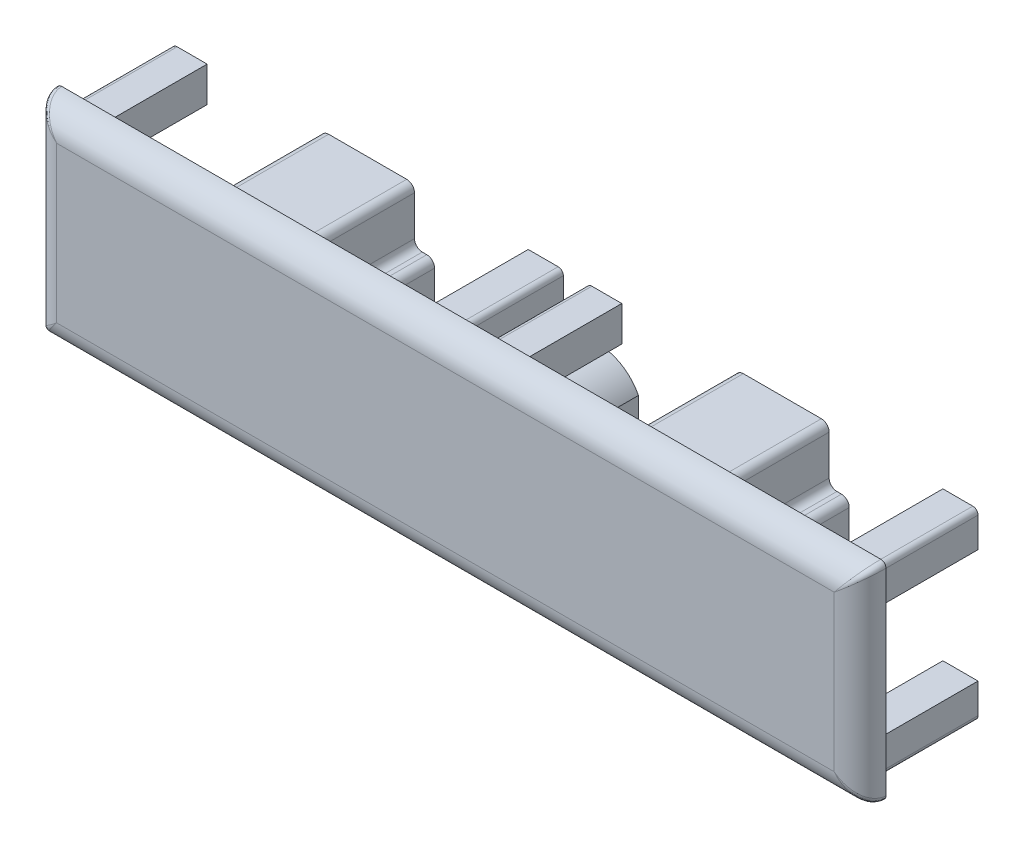
SolidWorks part; units mm, degrees
material "POLIURETAN (11671)"
ref_plane "Płaszczyzna przednia" through (0, 0, 0) normal (0, 0, 1) x (1, 0, 0)
ref_plane "Płaszczyzna górna" through (0, 0, 0) normal (0, 1, 0) x (1, 0, 0)
ref_plane "Płaszczyzna prawa" through (0, 0, 0) normal (1, 0, 0) x (0, 0, -1)
sketch "Szkic1" plane through (0, 0, 0) normal (0, 0, 1) x (1, 0, 0)
  line L0 (0, 20) -> (0, -20) construction
  line L1 (-40, 0) -> (40, 0) construction
  line L4 (-40, -20) -> (-40, 20)
  line L7 (-40, -20) -> (0, 0) construction
  line L8 (-40, 20) -> (40, -20) construction
  line L13 (20, 20) -> (20, 0) construction
  line L15 (24, 20) -> (24, 15.5)
  line L16 (24, 15.5) -> (26.4714, 15.5)
  line L21 (16, 15.5) -> (13.5286, 15.5)
  line L23 (16, 20) -> (13.5286, 20)
  line L24 (16, 20) -> (16, 15.5)
  line L25 (16, 7.75) -> (24, 7.75)
  line L26 (13.5286, 15.5) -> (13.5286, 17.75)
  line L27 (26.4714, 15.5) -> (26.4714, 17.75)
  line L28 (-24, 20) -> (-24, 15.5)
  line L29 (-26.4714, 15.5) -> (-26.4714, 17.75)
  line L30 (-24, 15.5) -> (-26.4714, 15.5)
  line L31 (-13.5286, 15.5) -> (-13.5286, 17.75)
  line L32 (-16, 15.5) -> (-13.5286, 15.5)
  line L33 (-16, 20) -> (-16, 15.5)
  line L34 (-16, 7.75) -> (-24, 7.75)
  line L35 (20, -20) -> (20, 0) construction
  line L36 (-40, -20) -> (0, 0) construction
  line L37 (-40, 20) -> (40, -20) construction
  line L39 (-16, -7.75) -> (-24, -7.75)
  line L40 (-16, -20) -> (-16, -15.5)
  line L41 (-16, -15.5) -> (-13.5286, -15.5)
  line L42 (-13.5286, -15.5) -> (-13.5286, -17.75)
  line L43 (-24, -15.5) -> (-26.4714, -15.5)
  line L44 (-26.4714, -15.5) -> (-26.4714, -17.75)
  line L45 (-24, -20) -> (-24, -15.5)
  line L46 (26.4714, -15.5) -> (26.4714, -17.75)
  line L47 (13.5286, -15.5) -> (13.5286, -17.75)
  line L48 (16, -7.75) -> (24, -7.75)
  line L49 (16, -20) -> (16, -15.5)
  line L50 (16, -15.5) -> (13.5286, -15.5)
  line L51 (24, -15.5) -> (26.4714, -15.5)
  line L52 (24, -20) -> (24, -15.5)
  line L53 (40, -20) -> (0, 20) construction
  line L54 (35.5, 6.4714) -> (37.75, 6.4714)
  line L55 (35.5, 4) -> (35.5, 6.4714)
  line L56 (40, 4) -> (35.5, 4)
  line L57 (40, -4) -> (35.5, -4)
  line L58 (35.5, -4) -> (35.5, -6.4714)
  line L59 (35.5, -6.4714) -> (37.75, -6.4714)
  line L60 (27.75, 4) -> (27.75, -4)
  line L61 (-35.5, -6.4714) -> (-37.75, -6.4714)
  line L62 (-37.75, -4) -> (-35.5, -4)
  line L63 (-35.5, -4) -> (-35.5, -6.4714)
  line L64 (-35.5, 4) -> (-35.5, 6.4714)
  line L65 (-35.5, 6.4714) -> (-37.75, 6.4714)
  line L66 (-37.75, 4) -> (-35.5, 4)
  line L67 (-27.75, 4) -> (-27.75, -4)
  line L68 (-37.75, 4) -> (-37.75, -4)
  line L69 (40, -4) -> (40, -16.6699)
  line L70 (40, 16.6699) -> (40, 4)
  line L71 (-40, -20) -> (-24, -20)
  line L72 (-16, -20) -> (16, -20)
  line L73 (24, -20) -> (36.6699, -20)
  line L74 (13.5286, 20) -> (-16, 20)
  line L75 (-24, 20) -> (-40, 20)
  line L76 (24, 20) -> (36.6699, 20)
  line L77 (10.5286, 7.0902) -> (11.4095, 7.0902)
  line L78 (-7.5286, -17.75) -> (7.5286, -17.75)
  line L79 (-9.0286, -16.25) -> (-9.0286, -8.5902)
  line L80 (-7.5286, 17.75) -> (7.5286, 17.75)
  line L81 (9.0286, -16.25) -> (9.0286, -8.5902)
  line L82 (-9.0286, -17.75) -> (9.0286, 17.75) construction
  line L83 (-9.0286, 17.75) -> (9.0286, -17.75) construction
  line L84 (-11.4095, -7.0902) -> (-10.5286, -7.0902)
  line L85 (-12.9095, -5.5902) -> (-12.9095, 5.5902)
  line L86 (-11.4095, 7.0902) -> (-10.5286, 7.0902)
  line L87 (12.9095, -5.5902) -> (12.9095, 5.5902)
  line L88 (-12.9095, -7.0902) -> (0, 0) construction
  line L89 (-12.9095, 7.0902) -> (12.9095, -7.0902) construction
  line L90 (-9.0286, 8.5902) -> (-9.0286, 16.25)
  line L91 (-9.0286, 4.5143) -> (-9.0286, 4.9587)
  line L92 (-9.0286, -4.9587) -> (-9.0286, -4.5143)
  line L93 (9.0286, 8.5902) -> (9.0286, 16.25)
  line L94 (10.5286, -7.0902) -> (11.4095, -7.0902)
  line L96 (0, 0) -> (12.9095, 7.0902) construction
  line L99 (30.9714, 10.9714) -> (37.75, 10.9714)
  line L100 (30.9714, 10.9714) -> (30.9714, 17.75)
  line L101 (30.9714, 17.75) -> (36.75, 17.75)
  line L102 (37.75, 10.9714) -> (37.75, 16.75)
  line L103 (30.9714, 10.9714) -> (37.75, 17.75) construction
  line L104 (30.9714, 17.75) -> (37.75, 10.9714) construction
  line L115 (-40, 52.1634) -> (-40, -64.8993) construction
  line L116 (-110.9714, 17.75) -> (-117.75, 10.9714) construction
  line L117 (-110.9714, 10.9714) -> (-117.75, 17.75) construction
  line L118 (-80, 0) -> (-92.9095, 7.0902) construction
  line L119 (-67.0905, 7.0902) -> (-92.9095, -7.0902) construction
  line L120 (-67.0905, -7.0902) -> (-80, 0) construction
  line L121 (-70.9714, 17.75) -> (-89.0286, -17.75) construction
  line L122 (-70.9714, -17.75) -> (-89.0286, 17.75) construction
  line L123 (-120, -20) -> (-80, 20) construction
  line L124 (-40, 20) -> (-120, -20) construction
  line L125 (-51.25, 3.7493) -> (-51.25, -3.7493)
  line L126 (-100, -20) -> (-100, 0) construction
  line L127 (-100, 20) -> (-100, 0) construction
  line L128 (-40, 20) -> (-120, -20) construction
  line L129 (-45.5, -7.4714) -> (-43.75, -7.4714)
  line L130 (-40, 0) -> (-120, 0) construction
  line L131 (-80, 20) -> (-80, -20) construction
  line L142 (-117.75, 10.9714) -> (-117.75, 16.75)
  line L143 (-110.9714, 17.75) -> (-116.75, 17.75)
  line L144 (-110.9714, 10.9714) -> (-110.9714, 17.75)
  line L145 (-110.9714, 10.9714) -> (-117.75, 10.9714)
  line L147 (-90.5286, -7.0902) -> (-91.4095, -7.0902)
  line L148 (-89.0286, 8.5902) -> (-89.0286, 16.25)
  line L149 (-70.9714, -4.9587) -> (-70.9714, -4.5143)
  line L150 (-70.9714, 4.5143) -> (-70.9714, 4.9587)
  line L151 (-70.9714, 8.5902) -> (-70.9714, 16.25)
  line L152 (-92.9095, -5.5902) -> (-92.9095, 5.5902)
  line L153 (-68.5905, 7.0902) -> (-69.4714, 7.0902)
  line L154 (-67.0905, -5.5902) -> (-67.0905, 5.5902)
  line L155 (-68.5905, -7.0902) -> (-69.4714, -7.0902)
  line L156 (-89.0286, -16.25) -> (-89.0286, -8.5902)
  line L157 (-72.4714, 17.75) -> (-87.5286, 17.75)
  line L158 (-70.9714, -16.25) -> (-70.9714, -8.5902)
  line L159 (-72.4714, -17.75) -> (-87.5286, -17.75)
  line L160 (-90.5286, 7.0902) -> (-91.4095, 7.0902)
  line L161 (-104, 20) -> (-116.6699, 20)
  line L162 (-56, 20) -> (-40, 20)
  line L163 (-93.5286, 20) -> (-64, 20)
  line L164 (-104, -20) -> (-116.6699, -20)
  line L165 (-64, -20) -> (-96, -20)
  line L166 (-40, -20) -> (-56, -20)
  line L167 (-120, 16.6699) -> (-120, 4)
  line L168 (-120, -4) -> (-120, -16.6699)
  line L169 (-42.25, 4) -> (-42.25, -4)
  line L170 (-52.25, 4) -> (-52.25, -4)
  line L171 (-42.25, 4) -> (-44.5, 4)
  line L172 (-44.5, 6.4714) -> (-42.25, 6.4714)
  line L173 (-44.5, 4) -> (-44.5, 6.4714)
  line L174 (-44.5, -4) -> (-44.5, -6.4714)
  line L175 (-42.25, -4) -> (-44.5, -4)
  line L176 (-44.5, -6.4714) -> (-42.25, -6.4714)
  line L177 (-107.75, 4) -> (-107.75, -4)
  line L178 (-115.5, -6.4714) -> (-117.75, -6.4714)
  line L179 (-115.5, -4) -> (-115.5, -6.4714)
  line L180 (-120, -4) -> (-115.5, -4)
  line L181 (-120, 4) -> (-115.5, 4)
  line L182 (-115.5, 4) -> (-115.5, 6.4714)
  line L183 (-115.5, 6.4714) -> (-117.75, 6.4714)
  line L184 (-104, -20) -> (-104, -15.5)
  line L185 (-104, -15.5) -> (-106.4714, -15.5)
  line L186 (-96, -15.5) -> (-93.5286, -15.5)
  line L187 (-96, -20) -> (-96, -15.5)
  line L188 (-96, -7.75) -> (-104, -7.75)
  line L189 (-93.5286, -15.5) -> (-93.5286, -17.75)
  line L190 (-106.4714, -15.5) -> (-106.4714, -17.75)
  line L191 (-56, -20) -> (-56, -15.5)
  line L192 (-53.5286, -15.5) -> (-53.5286, -17.75)
  line L193 (-56, -15.5) -> (-53.5286, -15.5)
  line L194 (-66.4714, -15.5) -> (-66.4714, -17.75)
  line L195 (-64, -15.5) -> (-66.4714, -15.5)
  line L196 (-64, -20) -> (-64, -15.5)
  line L197 (-64, -7.75) -> (-56, -7.75)
  line L199 (-64, 7.75) -> (-56, 7.75)
  line L200 (-64, 20) -> (-64, 15.5)
  line L201 (-64, 15.5) -> (-66.4714, 15.5)
  line L202 (-66.4714, 15.5) -> (-66.4714, 17.75)
  line L203 (-56, 15.5) -> (-53.5286, 15.5)
  line L204 (-53.5286, 15.5) -> (-53.5286, 17.75)
  line L205 (-56, 20) -> (-56, 15.5)
  line L206 (-106.4714, 15.5) -> (-106.4714, 17.75)
  line L207 (-93.5286, 15.5) -> (-93.5286, 17.75)
  line L208 (-96, 7.75) -> (-104, 7.75)
  line L209 (-96, 20) -> (-96, 15.5)
  line L210 (-96, 20) -> (-93.5286, 20)
  line L211 (-96, 15.5) -> (-93.5286, 15.5)
  line L212 (-104, 15.5) -> (-106.4714, 15.5)
  line L213 (-104, 20) -> (-104, 15.5)
  line L214 (-88.0286, 8.5902) -> (-88.0286, 16.25)
  line L215 (-45.5, -3) -> (-45.5, -7.4714)
  line L216 (-43.25, -3) -> (-45.5, -3)
  line L217 (-43.25, 3) -> (-43.25, -3)
  line L218 (-43.25, 3) -> (-45.5, 3)
  line L219 (-72.4714, 16.75) -> (-87.5286, 16.75)
  line L220 (-71.9714, 8.5902) -> (-71.9714, 16.25)
  line L221 (-68.5905, 6.0902) -> (-69.4714, 6.0902)
  line L222 (-68.0905, -5.5902) -> (-68.0905, 5.5902)
  line L223 (-68.5905, -6.0902) -> (-69.4714, -6.0902)
  line L224 (-71.9714, -16.25) -> (-71.9714, -8.5902)
  line L225 (-72.4714, -16.75) -> (-87.5286, -16.75)
  line L226 (-88.0286, -16.25) -> (-88.0286, -8.5902)
  line L227 (-90.5286, -6.0902) -> (-91.4095, -6.0902)
  line L228 (-91.9095, -5.5902) -> (-91.9095, 5.5902)
  line L229 (-90.5286, 6.0902) -> (-91.4095, 6.0902)
  line L254 (-45.5, 3) -> (-45.5, 7.4714)
  line L255 (-45.5, 7.4714) -> (-43.75, 7.4714)
  line L256 (-36.75, 3) -> (-36.75, -3)
  line L257 (-36.75, -3) -> (-34.5, -3)
  line L258 (-34.5, -3) -> (-34.5, -7.4714)
  line L259 (-34.5, -7.4714) -> (-36.25, -7.4714)
  line L260 (-30.9714, 10.9714) -> (-37.75, 10.9714)
  line L261 (-30.9714, 10.9714) -> (-30.9714, 17.75)
  line L266 (-30.9714, 17.75) -> (-36.75, 17.75)
  line L267 (-37.75, 10.9714) -> (-37.75, 16.75)
  line L332 (-28.75, 3.7493) -> (-28.75, -3.7493)
  line L333 (-34.5, 7.4714) -> (-36.25, 7.4714)
  line L334 (-34.5, 3) -> (-34.5, 7.4714)
  line L335 (-36.75, 3) -> (-34.5, 3)
  line L336 (-116.75, 11.9714) -> (-116.75, 16.75)
  line L337 (-111.9714, 11.9714) -> (-116.75, 11.9714)
  line L338 (-111.9714, 11.9714) -> (-111.9714, 16.75)
  line L339 (-111.9714, 16.75) -> (-116.75, 16.75)
  line L356 (-49.0286, 10.9714) -> (-49.0286, 17.75)
  line L357 (-49.0286, 17.75) -> (-43.25, 17.75)
  line L358 (-42.25, 10.9714) -> (-42.25, 16.75)
  line L359 (-49.0286, 10.9714) -> (-42.25, 10.9714)
  line L360 (31.9714, 11.9714) -> (31.9714, 16.75)
  line L361 (31.9714, 16.75) -> (36.75, 16.75)
  line L362 (36.75, 11.9714) -> (36.75, 16.75)
  line L363 (31.9714, 11.9714) -> (36.75, 11.9714)
  line L364 (-7.5286, 16.75) -> (7.5286, 16.75)
  line L365 (8.0286, 8.5902) -> (8.0286, 16.25)
  line L366 (10.5286, 6.0902) -> (11.4095, 6.0902)
  line L367 (11.9095, -5.5902) -> (11.9095, 5.5902)
  line L368 (10.5286, -6.0902) -> (11.4095, -6.0902)
  line L369 (8.0286, -16.25) -> (8.0286, -8.5902)
  line L370 (-7.5286, -16.75) -> (7.5286, -16.75)
  line L371 (-8.0286, -16.25) -> (-8.0286, -8.5902)
  line L372 (-11.4095, -6.0902) -> (-10.5286, -6.0902)
  line L373 (-11.9095, -5.5902) -> (-11.9095, 5.5902)
  line L374 (-11.4095, 6.0902) -> (-10.5286, 6.0902)
  line L375 (-8.0286, 8.5902) -> (-8.0286, 16.25)
  line L376 (30.9714, -17.75) -> (36.75, -17.75)
  line L377 (37.75, -10.9714) -> (37.75, -16.75)
  line L378 (30.9714, -10.9714) -> (37.75, -10.9714)
  line L379 (30.9714, -10.9714) -> (30.9714, -17.75)
  line L380 (-110.9714, -17.75) -> (-116.75, -17.75)
  line L381 (-110.9714, -10.9714) -> (-110.9714, -17.75)
  line L382 (-110.9714, -10.9714) -> (-117.75, -10.9714)
  line L383 (-117.75, -10.9714) -> (-117.75, -16.75)
  line L384 (-49.0286, -10.9714) -> (-42.25, -10.9714)
  line L385 (-42.25, -10.9714) -> (-42.25, -16.75)
  line L386 (-49.0286, -17.75) -> (-43.25, -17.75)
  line L387 (-49.0286, -10.9714) -> (-49.0286, -17.75)
  line L388 (-30.9714, -10.9714) -> (-30.9714, -17.75)
  line L389 (-30.9714, -17.75) -> (-36.75, -17.75)
  line L390 (-37.75, -10.9714) -> (-37.75, -16.75)
  line L391 (-30.9714, -10.9714) -> (-37.75, -10.9714)
  line L392 (-31.9714, 11.9714) -> (-36.75, 11.9714)
  line L393 (-36.75, 11.9714) -> (-36.75, 16.75)
  line L394 (-31.9714, 16.75) -> (-36.75, 16.75)
  line L395 (-31.9714, 11.9714) -> (-31.9714, 16.75)
  line L396 (-48.0286, 11.9714) -> (-48.0286, 16.75)
  line L397 (-48.0286, 16.75) -> (-43.25, 16.75)
  line L398 (-43.25, 11.9714) -> (-43.25, 16.75)
  line L399 (-48.0286, 11.9714) -> (-43.25, 11.9714)
  line L400 (-111.9714, -16.75) -> (-116.75, -16.75)
  line L401 (-116.75, -11.9714) -> (-116.75, -16.75)
  line L402 (-111.9714, -11.9714) -> (-116.75, -11.9714)
  line L403 (-111.9714, -11.9714) -> (-111.9714, -16.75)
  line L404 (-48.0286, -11.9714) -> (-43.25, -11.9714)
  line L405 (-43.25, -11.9714) -> (-43.25, -16.75)
  line L406 (-48.0286, -16.75) -> (-43.25, -16.75)
  line L407 (-48.0286, -11.9714) -> (-48.0286, -16.75)
  line L408 (-31.9714, -11.9714) -> (-31.9714, -16.75)
  line L409 (-31.9714, -16.75) -> (-36.75, -16.75)
  line L410 (-36.75, -11.9714) -> (-36.75, -16.75)
  line L411 (-31.9714, -11.9714) -> (-36.75, -11.9714)
  line L412 (31.9714, -16.75) -> (36.75, -16.75)
  line L413 (36.75, -11.9714) -> (36.75, -16.75)
  line L414 (31.9714, -11.9714) -> (36.75, -11.9714)
  line L415 (31.9714, -11.9714) -> (31.9714, -16.75)
  circle A0 centre (-20, 0) radius 3.4
  circle A1 centre (20, 0) radius 3.4
  arc A2 (26.4714, 17.75) -> (28.7214, 15.5) centre (26.4714, 15.5) cw
  arc A3 (28.7214, 15.5) -> (24, 7.75) centre (20, 15.5) cw
  arc A4 (13.5286, 17.75) -> (11.2786, 15.5) centre (13.5286, 15.5) ccw
  arc A5 (11.2786, 15.5) -> (16, 7.75) centre (20, 15.5) ccw
  arc A6 (-26.4714, 17.75) -> (-28.7214, 15.5) centre (-26.4714, 15.5) ccw
  arc A7 (-13.5286, 17.75) -> (-11.2786, 15.5) centre (-13.5286, 15.5) cw
  arc A8 (-11.2786, 15.5) -> (-16, 7.75) centre (-20, 15.5) cw
  arc A9 (-28.7214, 15.5) -> (-24, 7.75) centre (-20, 15.5) ccw
  arc A10 (-28.7214, -15.5) -> (-24, -7.75) centre (-20, -15.5) cw
  arc A11 (-11.2786, -15.5) -> (-16, -7.75) centre (-20, -15.5) ccw
  arc A12 (-13.5286, -17.75) -> (-11.2786, -15.5) centre (-13.5286, -15.5) ccw
  arc A13 (-26.4714, -17.75) -> (-28.7214, -15.5) centre (-26.4714, -15.5) cw
  arc A14 (11.2786, -15.5) -> (16, -7.75) centre (20, -15.5) cw
  arc A15 (13.5286, -17.75) -> (11.2786, -15.5) centre (13.5286, -15.5) cw
  arc A16 (28.7214, -15.5) -> (24, -7.75) centre (20, -15.5) ccw
  arc A17 (26.4714, -17.75) -> (28.7214, -15.5) centre (26.4714, -15.5) ccw
  arc A18 (35.5, 8.7214) -> (27.75, 4) centre (35.5, 0) ccw
  arc A19 (37.75, 6.4714) -> (35.5, 8.7214) centre (35.5, 6.4714) ccw
  arc A20 (37.75, -6.4714) -> (35.5, -8.7214) centre (35.5, -6.4714) cw
  arc A21 (35.5, -8.7214) -> (27.75, -4) centre (35.5, 0) cw
  arc A22 (-35.5, -8.7214) -> (-27.75, -4) centre (-35.5, 0) ccw
  arc A23 (-37.75, -6.4714) -> (-35.5, -8.7214) centre (-35.5, -6.4714) ccw
  arc A24 (-37.75, 6.4714) -> (-35.5, 8.7214) centre (-35.5, 6.4714) cw
  arc A25 (-35.5, 8.7214) -> (-27.75, 4) centre (-35.5, 0) cw
  arc A26 (-10.5286, 7.0902) -> (-9.0286, 8.5902) centre (-10.5286, 8.5902) ccw
  arc A27 (-9.0286, -8.5902) -> (-10.5286, -7.0902) centre (-10.5286, -8.5902) ccw
  arc A28 (11.4095, -7.0902) -> (12.9095, -5.5902) centre (11.4095, -5.5902) ccw
  arc A29 (9.0286, -8.5902) -> (10.5286, -7.0902) centre (10.5286, -8.5902) cw
  arc A30 (7.5286, -17.75) -> (9.0286, -16.25) centre (7.5286, -16.25) ccw
  arc A31 (-7.5286, -17.75) -> (-9.0286, -16.25) centre (-7.5286, -16.25) cw
  arc A32 (-11.4095, -7.0902) -> (-12.9095, -5.5902) centre (-11.4095, -5.5902) cw
  arc A33 (-12.9095, 5.5902) -> (-11.4095, 7.0902) centre (-11.4095, 5.5902) cw
  arc A34 (-9.0286, 16.25) -> (-7.5286, 17.75) centre (-7.5286, 16.25) cw
  arc A35 (7.5286, 17.75) -> (9.0286, 16.25) centre (7.5286, 16.25) cw
  arc A36 (11.4095, 7.0902) -> (12.9095, 5.5902) centre (11.4095, 5.5902) cw
  arc A37 (10.5286, 7.0902) -> (9.0286, 8.5902) centre (10.5286, 8.5902) cw
  arc A40 (36.6699, -20) -> (40, -16.6699) centre (36.6699, -16.6699) ccw
  arc A41 (36.6699, 20) -> (40, 16.6699) centre (36.6699, 16.6699) cw
  arc A42 (36.75, 17.75) -> (37.75, 16.75) centre (36.75, 16.75) cw
  arc A49 (-116.75, 17.75) -> (-117.75, 16.75) centre (-116.75, 16.75) ccw
  arc A50 (-116.6699, 20) -> (-120, 16.6699) centre (-116.6699, 16.6699) ccw
  arc A51 (-116.6699, -20) -> (-120, -16.6699) centre (-116.6699, -16.6699) cw
  arc A53 (-90.5286, 6.0902) -> (-88.0286, 8.5902) centre (-90.5286, 8.5902) ccw
  arc A54 (-90.5286, 7.0902) -> (-89.0286, 8.5902) centre (-90.5286, 8.5902) ccw
  arc A55 (-91.4095, 7.0902) -> (-92.9095, 5.5902) centre (-91.4095, 5.5902) ccw
  arc A56 (-87.5286, 17.75) -> (-89.0286, 16.25) centre (-87.5286, 16.25) ccw
  arc A57 (-70.9714, 16.25) -> (-72.4714, 17.75) centre (-72.4714, 16.25) ccw
  arc A58 (-67.0905, 5.5902) -> (-68.5905, 7.0902) centre (-68.5905, 5.5902) ccw
  arc A59 (-68.5905, -7.0902) -> (-67.0905, -5.5902) centre (-68.5905, -5.5902) ccw
  arc A60 (-72.4714, -17.75) -> (-70.9714, -16.25) centre (-72.4714, -16.25) ccw
  arc A61 (-87.5286, -17.75) -> (-89.0286, -16.25) centre (-87.5286, -16.25) cw
  arc A62 (-89.0286, -8.5902) -> (-90.5286, -7.0902) centre (-90.5286, -8.5902) ccw
  arc A63 (-91.4095, -7.0902) -> (-92.9095, -5.5902) centre (-91.4095, -5.5902) cw
  arc A64 (-70.9714, -8.5902) -> (-69.4714, -7.0902) centre (-69.4714, -8.5902) cw
  arc A65 (-69.4714, 7.0902) -> (-70.9714, 8.5902) centre (-69.4714, 8.5902) cw
  arc A66 (-44.5, 8.7214) -> (-52.25, 4) centre (-44.5, 0) ccw
  arc A67 (-42.25, 6.4714) -> (-44.5, 8.7214) centre (-44.5, 6.4714) ccw
  arc A68 (-42.25, -6.4714) -> (-44.5, -8.7214) centre (-44.5, -6.4714) cw
  arc A69 (-44.5, -8.7214) -> (-52.25, -4) centre (-44.5, 0) cw
  arc A70 (-115.5, -8.7214) -> (-107.75, -4) centre (-115.5, 0) ccw
  arc A71 (-117.75, -6.4714) -> (-115.5, -8.7214) centre (-115.5, -6.4714) ccw
  arc A72 (-117.75, 6.4714) -> (-115.5, 8.7214) centre (-115.5, 6.4714) cw
  arc A73 (-115.5, 8.7214) -> (-107.75, 4) centre (-115.5, 0) cw
  arc A74 (-106.4714, -17.75) -> (-108.7214, -15.5) centre (-106.4714, -15.5) cw
  arc A75 (-108.7214, -15.5) -> (-104, -7.75) centre (-100, -15.5) cw
  arc A76 (-93.5286, -17.75) -> (-91.2786, -15.5) centre (-93.5286, -15.5) ccw
  arc A77 (-91.2786, -15.5) -> (-96, -7.75) centre (-100, -15.5) ccw
  arc A78 (-53.5286, -17.75) -> (-51.2786, -15.5) centre (-53.5286, -15.5) ccw
  arc A79 (-66.4714, -17.75) -> (-68.7214, -15.5) centre (-66.4714, -15.5) cw
  arc A80 (-68.7214, -15.5) -> (-64, -7.75) centre (-60, -15.5) cw
  arc A81 (-51.2786, -15.5) -> (-56, -7.75) centre (-60, -15.5) ccw
  arc A82 (-51.2786, 15.5) -> (-56, 7.75) centre (-60, 15.5) cw
  arc A83 (-68.7214, 15.5) -> (-64, 7.75) centre (-60, 15.5) ccw
  arc A84 (-66.4714, 17.75) -> (-68.7214, 15.5) centre (-66.4714, 15.5) ccw
  arc A85 (-53.5286, 17.75) -> (-51.2786, 15.5) centre (-53.5286, 15.5) cw
  arc A86 (-91.2786, 15.5) -> (-96, 7.75) centre (-100, 15.5) cw
  arc A87 (-93.5286, 17.75) -> (-91.2786, 15.5) centre (-93.5286, 15.5) cw
  arc A88 (-108.7214, 15.5) -> (-104, 7.75) centre (-100, 15.5) ccw
  arc A89 (-106.4714, 17.75) -> (-108.7214, 15.5) centre (-106.4714, 15.5) ccw
  circle A90 centre (-100, 0) radius 3.4
  circle A91 centre (-60, 0) radius 3.4
  arc A92 (-87.5286, 16.75) -> (-88.0286, 16.25) centre (-87.5286, 16.25) ccw
  arc A93 (-71.9714, 16.25) -> (-72.4714, 16.75) centre (-72.4714, 16.25) ccw
  arc A94 (-69.4714, 6.0902) -> (-71.9714, 8.5902) centre (-69.4714, 8.5902) cw
  arc A95 (-68.0905, 5.5902) -> (-68.5905, 6.0902) centre (-68.5905, 5.5902) ccw
  arc A96 (-68.5905, -6.0902) -> (-68.0905, -5.5902) centre (-68.5905, -5.5902) ccw
  arc A97 (-71.9714, -8.5902) -> (-69.4714, -6.0902) centre (-69.4714, -8.5902) cw
  arc A98 (-72.4714, -16.75) -> (-71.9714, -16.25) centre (-72.4714, -16.25) ccw
  arc A99 (-87.5286, -16.75) -> (-88.0286, -16.25) centre (-87.5286, -16.25) cw
  arc A100 (-88.0286, -8.5902) -> (-90.5286, -6.0902) centre (-90.5286, -8.5902) ccw
  arc A101 (-91.4095, -6.0902) -> (-91.9095, -5.5902) centre (-91.4095, -5.5902) cw
  arc A102 (-91.4095, 6.0902) -> (-91.9095, 5.5902) centre (-91.4095, 5.5902) ccw
  circle A103 centre (-100, 0) radius 2.4
  arc A115 (-44.5, 7.7214) -> (-51.25, 3.7493) centre (-44.5, 0) ccw
  arc A116 (-44.5, -7.7214) -> (-51.25, -3.7493) centre (-44.5, 0) cw
  arc A119 (-43.75, -7.4714) -> (-44.5, -7.7214) centre (-44.5, -6.4714) cw
  circle A132 centre (20, 0) radius 2.4
  arc A135 (-43.75, 7.4714) -> (-44.5, 7.7214) centre (-44.5, 6.4714) ccw
  arc A136 (-36.25, -7.4714) -> (-35.5, -7.7214) centre (-35.5, -6.4714) ccw
  arc A137 (-35.5, -7.7214) -> (-28.75, -3.7493) centre (-35.5, 0) ccw
  arc A138 (-35.5, 7.7214) -> (-28.75, 3.7493) centre (-35.5, 0) cw
  arc A139 (-36.25, 7.4714) -> (-35.5, 7.7214) centre (-35.5, 6.4714) cw
  circle A140 centre (-60, 0) radius 2.4
  circle A141 centre (-20, 0) radius 2.4
  arc A142 (-36.75, 17.75) -> (-37.75, 16.75) centre (-36.75, 16.75) ccw
  arc A146 (-116.75, 16.75) -> (-116.75, 16.75) centre (-116.75, 16.75) ccw
  arc A149 (-43.25, 17.75) -> (-42.25, 16.75) centre (-43.25, 16.75) cw
  arc A150 (36.75, 16.75) -> (36.75, 16.75) centre (36.75, 16.75) cw
  arc A151 (7.5286, 16.75) -> (8.0286, 16.25) centre (7.5286, 16.25) cw
  arc A152 (10.5286, 6.0902) -> (8.0286, 8.5902) centre (10.5286, 8.5902) cw
  arc A153 (11.4095, 6.0902) -> (11.9095, 5.5902) centre (11.4095, 5.5902) cw
  arc A178 (11.4095, -6.0902) -> (11.9095, -5.5902) centre (11.4095, -5.5902) ccw
  arc A179 (8.0286, -8.5902) -> (10.5286, -6.0902) centre (10.5286, -8.5902) cw
  arc A180 (7.5286, -16.75) -> (8.0286, -16.25) centre (7.5286, -16.25) ccw
  arc A181 (-7.5286, -16.75) -> (-8.0286, -16.25) centre (-7.5286, -16.25) cw
  arc A182 (-8.0286, -8.5902) -> (-10.5286, -6.0902) centre (-10.5286, -8.5902) ccw
  arc A183 (-11.4095, -6.0902) -> (-11.9095, -5.5902) centre (-11.4095, -5.5902) cw
  arc A184 (-11.9095, 5.5902) -> (-11.4095, 6.0902) centre (-11.4095, 5.5902) cw
  arc A185 (-10.5286, 6.0902) -> (-8.0286, 8.5902) centre (-10.5286, 8.5902) ccw
  arc A186 (-8.0286, 16.25) -> (-7.5286, 16.75) centre (-7.5286, 16.25) cw
  arc A187 (36.75, -17.75) -> (37.75, -16.75) centre (36.75, -16.75) ccw
  arc A188 (-116.75, -17.75) -> (-117.75, -16.75) centre (-116.75, -16.75) cw
  arc A189 (-43.25, -17.75) -> (-42.25, -16.75) centre (-43.25, -16.75) ccw
  arc A190 (-36.75, -17.75) -> (-37.75, -16.75) centre (-36.75, -16.75) cw
  arc A191 (-36.75, 16.75) -> (-36.75, 16.75) centre (-36.75, 16.75) ccw
  arc A192 (-43.25, 16.75) -> (-43.25, 16.75) centre (-43.25, 16.75) cw
  arc A193 (-116.75, -16.75) -> (-116.75, -16.75) centre (-116.75, -16.75) cw
  arc A194 (-43.25, -16.75) -> (-43.25, -16.75) centre (-43.25, -16.75) ccw
  arc A195 (-36.75, -16.75) -> (-36.75, -16.75) centre (-36.75, -16.75) cw
  arc A196 (36.75, -16.75) -> (36.75, -16.75) centre (36.75, -16.75) ccw
  point P5 (0, 0)
  point P17 (0, 0)
  point P30 (24, 17.75)
  point P108 (0, 0)
  point P124 (-9.0286, 7.0902)
  point P132 (9.0286, -7.0902)
  point P156 (9.0286, 7.0902)
  point P161 (40, 20)
  point P162 (34.3607, 14.3607)
  point P364 (-114.3607, 14.3607)
  point P365 (-120, 20)
  point P366 (-89.0286, 7.0902)
  point P367 (-89.0286, -7.0902)
  point P368 (-70.9714, 7.0902)
  point P369 (-80, 0)
  point P370 (-80, 0)
  point P371 (-80, 0)
  dimension "D4" = 6.8
  dimension "D5" = 12.25
  dimension "D9" = 11
  dimension "D11" = 1.5
  dimension "D12" = 1
  dimension "D16" = 1
  dimension "D20" = 1
  dimension "D26" = 1
  dimension "D30" = 4.8
  dimension "D18" = 3.3301
  dimension "D1" = 80
  dimension "D2" = 40
  dimension "D3" = 40
  dimension "D6" = 2.25
  dimension "D7" = 8
  dimension "D8" = 4.5
  dimension "D10" = 14.1804
  dimension "D13" = 2.25
  dimension "D14" = 2.25
  dimension "D15" = 2.25
  dimension "D19" = 1
  dimension "D21" = 1
  dimension "D22" = 1
  dimension "D23" = 1
  dimension "D24" = 1
  dimension "D25" = 1
  dimension "D27" = 1
  dimension "D28" = 1
  dimension "D29" = 1
  dimension "D31" = 1
  dimension "D32" = 1
  dimension "D17" = 1
extrude "Dodanie-wyciągnięcie1" add sketch "Szkic1" along normal blind 20 contours L153 A65 L151 A57 L157 A56 L148 A54 L160 A55 L152 A63 L147 A62 L156 A61 L159 A60 L158 A64 L155 A59 L154 A58 A102 L229 A53 L214 A92 L219 A93 L220 A94 L221 A95 L222 A96 L223 A97 L224 A98 L225 A99 L226 A100 L227 A101 L228 | A90 A103 | L143 A49 L142 L145 L144 L339 L338 L337 L336 | A188 L380 L381 L382 L383 L402 L403 L400 L401 | A91 A140 | A149 L357 L356 L359 L358 L399 L396 L397 L398 | A69 A68 L176 L174 L175 L169 L171 L173 L172 A67 A66 L170 A135 L255 L254 L218 L217 L216 L215 L129 A119 A116 L125 A115 | L386 A189 L385 L384 L387 L407 L404 L405 L406 | A190 L389 L388 L391 L390 L411 L408 L409 L410 | L266 A142 L267 L260 L261 L395 L392 L393 L394 | A25 A24 L65 L64 L66 L68 L62 L63 L61 A23 A22 L67 L333 A139 A138 L332 A137 A136 L259 L258 L257 L256 L335 L334 | A0 A141 | L77 A37 L93 A35 L80 A34 L90 A26 L86 A33 L85 A32 L84 A27 L79 A31 L78 A30 L81 A29 L94 A28 L87 A36 L375 A186 L364 A151 L365 A152 L366 A153 L367 A178 L368 A179 L369 A180 L370 A181 L371 A182 L372 A183 L373 A184 L374 A185 | A1 A132 | A42 L101 L100 L99 L102 L363 L360 L361 L362 | L376 A187 L377 L378 L379 L415 L414 L413 L412 region at (-35.2989, -5.2357, 0) region at (10.9691, 6.6512, 0) region at (31.0672, 14.3607, 0) region at (-117.6541, 13.8607, 0) region at (-90.9691, -6.6512, 0) region at (-42.4511, 0, 0) region at (-34.3607, 11.0672, 0) region at (-48.9328, 14.3607, 0) region at (31.0672, -14.3607, 0) region at (-113.8607, -17.6541, 0) region at (-45.6393, -11.0672, 0) region at (-31.0672, -14.3607, 0) region at (-23.3038, 0, 0) region at (16.6962, 0, 0) region at (-103.3038, 0, 0) region at (-63.3038, 0, 0)
sketch "Szkic2" plane through (0, 0, 20) normal (0, 0, 1) x (1, 0, 0)
  line L0 (-40, -20) -> (-40, 20) construction
  line L1 (-119, -20) -> (39, -20)
  line L2 (-120, -19) -> (-120, 19)
  line L3 (-119, 20) -> (39, 20)
  line L4 (40, -19) -> (40, 19)
  line L5 (-120, -20) -> (40, 20) construction
  line L6 (-120, 20) -> (40, -20) construction
  line L7 (-40, 0) -> (40, 0) construction
  arc A0 (39, -20) -> (40, -19) centre (39, -19) ccw
  arc A1 (39, 20) -> (40, 19) centre (39, 19) cw
  arc A2 (-120, 19) -> (-119, 20) centre (-119, 19) cw
  arc A3 (-119, -20) -> (-120, -19) centre (-119, -19) cw
  point P0 (-40, 0)
  dimension "D3" = 1
  dimension "D1" = 160
  dimension "D2" = 40
extrude "Dodanie-wyciągnięcie2" add sketch "Szkic2" along normal blind 5
fillet "Zaokrąglenie1" radius 5 8 edges at (-40, -20, 25) (-119.7071, -19.7071, 25) (-120, 0, 25) (-119.7071, 19.7071, 25) (-40, 20, 25) (39.7071, 19.7071, 25) (40, 0, 25) (39.7071, -19.7071, 25)
